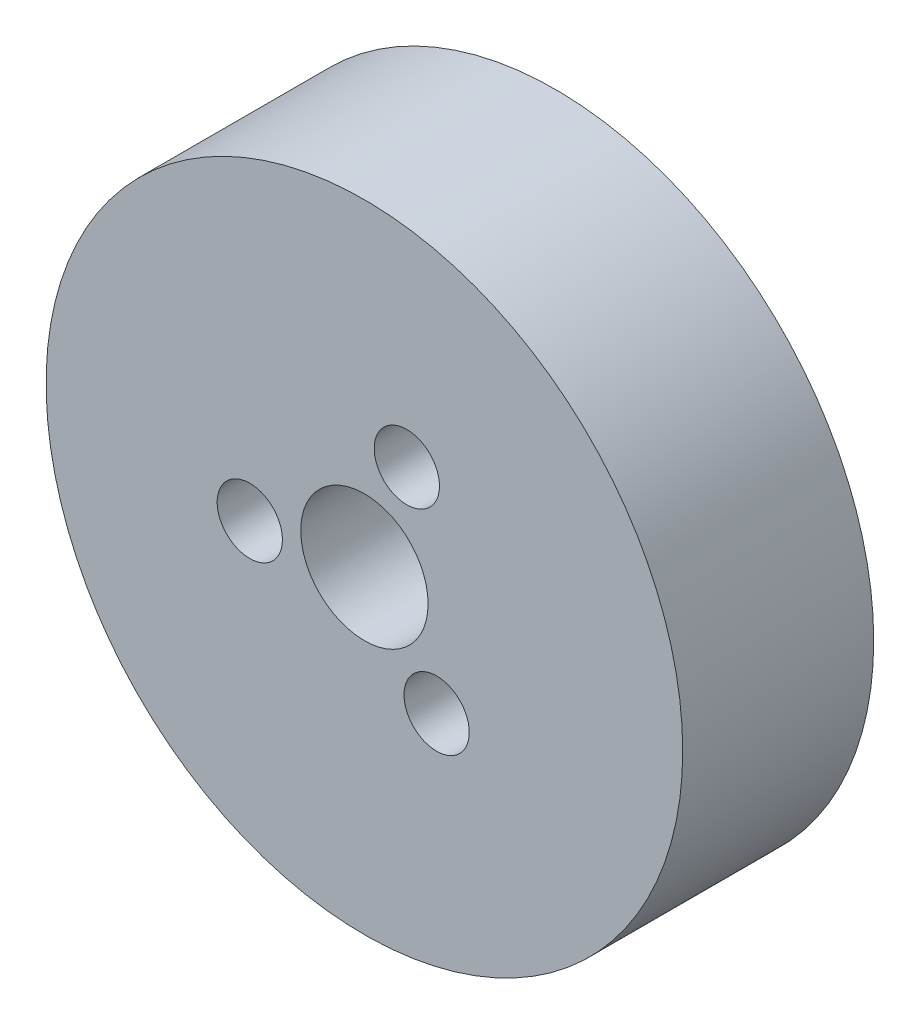
SolidWorks part; units mm, degrees
ref_plane "Front Plane" through (0, 0, 0) normal (0, 0, 1) x (1, 0, 0)
ref_plane "Top Plane" through (0, 0, 0) normal (0, 1, 0) x (1, 0, 0)
ref_plane "Right Plane" through (0, 0, 0) normal (1, 0, 0) x (0, 0, -1)
sketch "Sketch1" plane through (0, 0, 0) normal (0, 0, 1) x (1, 0, 0)
  circle A0 centre (0, 0) radius 10
  circle A1 centre (0, 0) radius 2
  dimension "D1" = 4
  dimension "D2" = 20
extrude "Boss-Extrude1" add sketch "Sketch1" along normal blind 6
hole_wizard "Ø2.05 (2.05) Diameter Hole1" positions "Sketch2" profile "Sketch3" hole size "Ø2.05" standard "ISO" end condition through all
sketch "Sketch2" plane through (-166.2191, 17.5479, 8.7955) normal (0, 0, 1) x (0.0629, -0.998, 0)
  circle A0 centre (27.9652, 164.7867) radius 3.6413
  point P0 (24.667, 166.3298)
  point P2 (30.9507, 166.8714)
  point P4 (28.2779, 161.1589)
sketch "Sketch3" plane through (1.3327, 3.3887, 8.7955) normal (1, 0, 0) x (0, -1, 0)
  line L0 (0, 0) -> (0, 8.7955)
  line L1 (0, 8.7955) -> (1.025, 8.7955)
  line L2 (1.025, 8.7955) -> (1.025, 0)
  line L3 (1.025, 0) -> (0, 0)
  line L4 (0, -6.35) -> (0, 107.95) construction
  dimension "Thru Hole Dia." = 2.05
  dimension "Thru Hole Depth" = 8.7955
